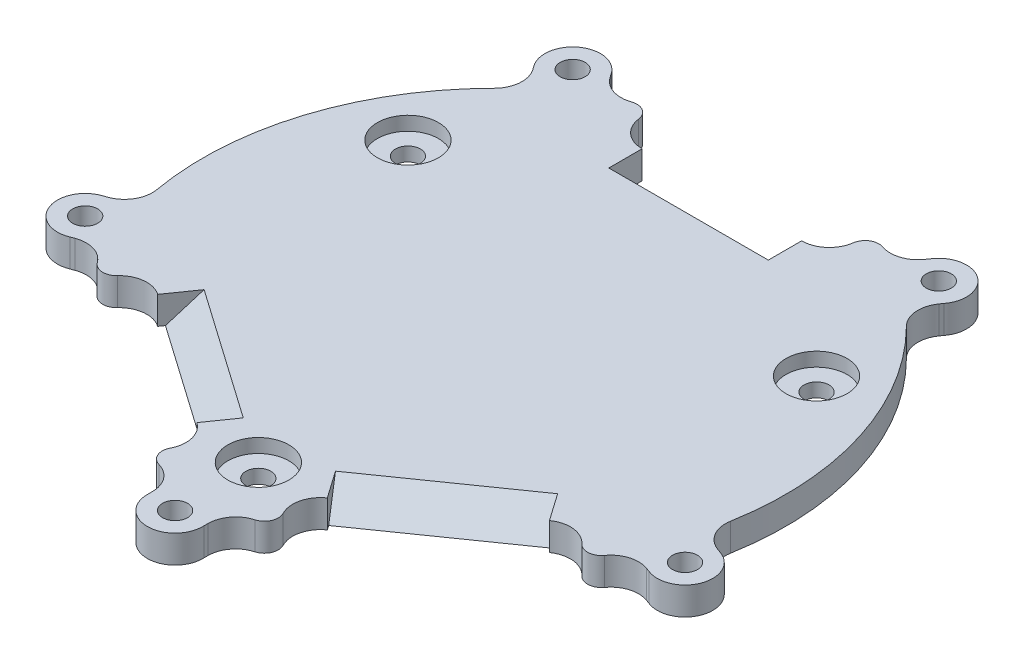
SolidWorks part; units mm, degrees
ref_plane "Plan de face" through (0, 0, 0) normal (0, 0, 1) x (1, 0, 0)
ref_plane "Plan de dessus" through (0, 0, 0) normal (0, 1, 0) x (1, 0, 0)
ref_plane "Plan de droite" through (0, 0, 0) normal (1, 0, 0) x (0, 0, -1)
sketch "Sketch1" plane through (0, 0, 0) normal (0, 1, 0) x (1, 0, 0)
  line L0 (0, 0) -> (0, 41) construction
  line L1 (0, 0) -> (-23.5166, -33.5852) construction
  line L2 (0, 0) -> (23.5166, -33.5852) construction
  line L3 (-39.3263, -22.5152) -> (-7.707, -44.6553)
  line L4 (7.707, -44.6553) -> (39.3263, -22.5152)
  line L5 (-19.3, 41) -> (19.3, 41)
  line L6 (-19.3, 41) -> (-19.3, 48.8238)
  line L8 (19.3, 41) -> (19.3, 48.8238)
  line L9 (7.707, -44.6553) -> (12.1945, -51.0641)
  line L11 (39.3263, -22.5152) -> (43.8138, -28.9241)
  line L12 (-7.707, -44.6553) -> (-12.1945, -51.0641)
  line L13 (-39.3263, -22.5152) -> (-43.8138, -28.9241)
  line L14 (0, 0) -> (0, -42.5) construction
  line L15 (0, 0) -> (-36.8061, 21.25) construction
  line L16 (0, 0) -> (36.8061, 21.25) construction
  arc A0 (-19.3, 48.8238) -> (-43.8138, -28.9241) centre (0, 0) ccw
  arc A1 (43.8138, -28.9241) -> (19.3, 48.8238) centre (0, 0) ccw
  circle A3 centre (-36.8061, 21.25) radius 2.25 construction
  circle A4 centre (36.8061, 21.25) radius 2.25 construction
  circle A6 centre (0, -42.5) radius 2.25 construction
  arc A7 (-12.1945, -51.0641) -> (12.1945, -51.0641) centre (0, 0) ccw
  circle A8 centre (-36.8061, 21.25) radius 5.5
  circle A9 centre (36.8061, 21.25) radius 5.5
  circle A10 centre (0, -42.5) radius 5.5
  point P25 (23.5166, -33.5852)
  point P26 (-23.5166, -33.5852)
  dimension "D1" = 105
  dimension "D5" = 35
  dimension "D6" = 38.6
  dimension "D10" = 4.5
  dimension "D4" = 11
  dimension "D9" = 42.5
  dimension "D2" = 35
  dimension "D3" = 41
  dimension "D7" = 120
  dimension "D8" = 120
extrude "Boss-Extrude1" add sketch "Sketch1" along normal blind 5 contours L4 A0 L5 L3 | A8 | A9 | A10 region at (0, 0, -1.6314) region at (-36.8061, 0, -21.25) region at (36.8061, 0, -21.25) region at (0, 0, 42.5)
extrude "Enlèv. mat.-Extru.3" cut sketch "Sketch1<3>" against normal blind 2.5 from surface contours A8 | A9 | A10 region at (-36.8061, 0, -21.25) region at (36.8061, 0, -21.25) region at (0, 0, 42.5) starting at face at (0, 5, 8.7026)
sketch "Sketch1<3>" plane through (0, 0, 0) normal (0, 1, 0) x (1, 0, 0) same geometry as "Sketch1"
hole_wizard "M4 Clearance Hole1" positions "Esquisse4" profile "Esquisse3" hole size "M4" standard "ANSI Metric" end condition up to next
sketch "Esquisse4" plane through (0, 5, 0) normal (0, 1, 0) x (1, 0, 0)
  point P0 (0, -42.5)
  point P3 (36.8061, 21.25)
  point P6 (-36.8061, 21.25)
sketch "Esquisse3" plane through (0, 5, 42.5) normal (1, 0, 0) x (0, 0, 1)
  line L0 (0, 0) -> (0, 5)
  line L1 (0, 5) -> (2.25, 5)
  line L2 (2.25, 5) -> (2.25, 0)
  line L5 (2.25, 0) -> (0, 0)
  line L11 (0, -6.35) -> (0, 107.95) construction
  dimension "Thru Hole Dia." = 4.5
  dimension "Thru Hole Depth" = 5
fillet "Congé1" radius 2.5 6 edges at (19.3, 2.5, -48.8238) (-19.3, 2.5, -48.8238) (-43.8138, 2.5, 28.9241) (43.8138, 2.5, 28.9241) (12.1945, 2.5, 51.0641) (-12.1945, 2.5, 51.0641)
sketch "Esquisse5" plane through (0, 5, 0) normal (0, 1, 0) x (1, 0, 0)
  line L0 (0, 0) -> (0, -57.5) construction
  line L1 (0, 0) -> (54.0323, -19.6662) construction
  line L2 (0, 0) -> (32.9806, 47.1012) construction
  line L3 (0, 0) -> (-32.9806, 47.1012) construction
  line L4 (0, 0) -> (-54.0323, -19.6662) construction
  line L5 (-52.1196, -24.2858) -> (-47.4016, -22.5686)
  line L6 (-55.5365, -14.8978) -> (-50.8185, -13.1806)
  line L7 (-36.9478, 44.058) -> (-34.068, 39.9452)
  line L8 (-28.7641, 49.7883) -> (-25.8843, 45.6755)
  line L9 (36.9478, 44.058) -> (34.068, 39.9452)
  line L10 (28.7641, 49.7883) -> (25.8843, 45.6755)
  line L11 (52.1196, -24.2858) -> (47.4016, -22.5686)
  line L12 (55.5365, -14.8978) -> (50.8185, -13.1806)
  line L13 (4.9953, -57.2826) -> (4.9953, -52.2618)
  line L14 (-4.9953, -57.2826) -> (-4.9953, -52.2618)
  arc A0 (-4.9953, -57.2826) -> (-52.1196, -24.2858) centre (0, 0) ccw construction
  arc A1 (52.1196, -24.2858) -> (55.5365, -14.8978) centre (54.0323, -19.6662) ccw
  arc A2 (-4.9953, -57.2826) -> (4.9953, -57.2826) centre (0, -57.5) ccw
  arc A3 (-55.5365, -14.8978) -> (-52.1196, -24.2858) centre (-54.0323, -19.6662) ccw
  arc A4 (-28.7641, 49.7883) -> (-36.9478, 44.058) centre (-32.9806, 47.1012) ccw
  arc A5 (36.9478, 44.058) -> (28.7641, 49.7883) centre (32.9806, 47.1012) ccw
  arc A6 (-8.3495, -51.8318) -> (8.3495, -51.8318) centre (0, 0) ccw construction
  arc A7 (-22.89, 47.2472) -> (-45.8503, -25.5735) centre (0, 0) ccw construction
  arc A8 (45.8503, -25.5735) -> (22.89, 47.2472) centre (0, 0) ccw construction
  arc A9 (-8.3495, -51.8318) -> (8.3495, -51.8318) centre (0, 0) ccw construction
  arc A10 (47.4016, -22.5686) -> (50.8185, -13.1806) centre (0, 0) ccw
  arc A11 (34.068, 39.9452) -> (25.8843, 45.6755) centre (0, 0) ccw
  arc A12 (-25.8843, 45.6755) -> (-34.068, 39.9452) centre (0, 0) ccw
  arc A13 (-50.8185, -13.1806) -> (-47.4016, -22.5686) centre (0, 0) ccw
  arc A14 (-4.9953, -52.2618) -> (4.9953, -52.2618) centre (0, 0) ccw
  dimension "D1" = 70
  dimension "D5" = 10
  dimension "D2" = 70
  dimension "D3" = 75
  dimension "D4" = 75
extrude "Boss.-Extru.1" add sketch "Esquisse5" against normal up to surface (5 mm away) up to face at (0, 0, 44.75)
hole_wizard "M4 Clearance Hole2" positions "Esquisse8" profile "Esquisse7" hole size "M4" standard "ANSI Metric" end condition up to next
sketch "Esquisse8" plane through (0, 5, 0) normal (0, 1, 0) x (1, 0, 0)
  point P0 (0, -57.5)
  point P3 (54.0323, -19.6662)
  point P6 (32.9806, 47.1012)
  point P9 (-32.9806, 47.1012)
  point P12 (-54.0323, -19.6662)
sketch "Esquisse7" plane through (0, 5, 57.5) normal (1, 0, 0) x (0, 0, 1)
  line L0 (0, 0) -> (0, 5)
  line L1 (0, 5) -> (2.25, 5)
  line L2 (2.25, 5) -> (2.25, 0)
  line L5 (2.25, 0) -> (0, 0)
  line L11 (0, -6.35) -> (0, 107.95) construction
  dimension "Thru Hole Dia." = 4.5
  dimension "Thru Hole Depth" = 5
fillet "Congé2" radius 5 16 edges at (47.4016, 2.5, 22.5686) (50.8185, 2.5, 13.1806) (34.068, 2.5, -39.9452) (-34.068, 2.5, -39.9452) (-50.8185, 2.5, 13.1806) (-47.4016, 2.5, 22.5686) (4.9953, 2.5, 52.2618) (-4.9953, 2.5, 52.2618) (25.8843, 2.5, -45.6755) (-25.8843, 2.5, -45.6755) (-7.707, 2.5, 44.6553) (-39.3263, 2.5, 22.5152) (-19.3, 2.5, -41) (19.3, 2.5, -41) (39.3263, 2.5, 22.5152) (7.707, 2.5, 44.6553)
ref_plane "Plan1" through (11.769, 0, 8.2408) normal (0.8192, 0, 0.5736) x (0, 1, 0)
sketch "Esquisse9" plane through (11.769, 0, 8.2408) normal (0.8192, 0, 0.5736) x (0, 1, 0)
  line L4 (5, 44.8512) -> (5, 49.3512) construction
  line L8 (0, 41) -> (5, 41) construction
  line L9 (0, 41) -> (5, 41)
  line L10 (5, 41) -> (5, 35)
  line L11 (5, 35) -> (0, 40)
  line L12 (0, 40) -> (0, 41)
  line L13 (0, 49.3512) -> (0, 44.8512) construction
  dimension "D1" = 1
  dimension "D2" = 45
extrude "Enlèv. mat.-Extru.4" cut sketch "Esquisse9" against normal up to vertex (28.7346 mm away) up to point (-35.2857, 5, 25.3445)
ref_plane "Plan2" through (-11.769, 0, 8.2408) normal (-0.8192, 0, 0.5736) x (0, -1, 0)
sketch "Esquisse10" plane through (-11.769, 0, 8.2408) normal (-0.8192, 0, 0.5736) x (0, -1, 0)
  line L0 (-5, 41) -> (-5, 35)
  line L1 (-5, 35) -> (0, 40)
  line L2 (0, 40) -> (0, 41)
  line L3 (0, 41) -> (-5, 41)
  line L4 (-5, -1.5302) -> (-5, 0.522) construction
  line L5 (-5, 41) -> (0, 41) construction
  line L6 (0, 44.8512) -> (0, 49.3512) construction
  dimension "D1" = 1
  dimension "D2" = 45
extrude "Enlèv. mat.-Extru.5" cut sketch "Esquisse10" against normal up to vertex (28.7346 mm away) up to point (35.2857, 5, 25.3445)
ref_plane "Plan3" through (-14.3673, 0, 0) normal (-1, 0, 0) x (0, 1, 0)
sketch "Esquisse11" plane through (-14.3673, 0, 0) normal (-1, 0, 0) x (0, 1, 0)
  line L0 (0, 41) -> (5, 41)
  line L1 (5, 41) -> (5, 35)
  line L2 (5, 35) -> (0, 40)
  line L3 (0, 40) -> (0, 41)
  line L5 (5, -59.75) -> (5, -55.25) construction
  line L6 (0, 23.5) -> (0, 19) construction
  line L8 (0, 41) -> (5, 41) construction
  dimension "D1" = 1
  dimension "D2" = 45
extrude "Enlèv. mat.-Extru.6" cut sketch "Esquisse11" against normal up to vertex (28.7346 mm away) up to point (14.3673, 5, -41)
